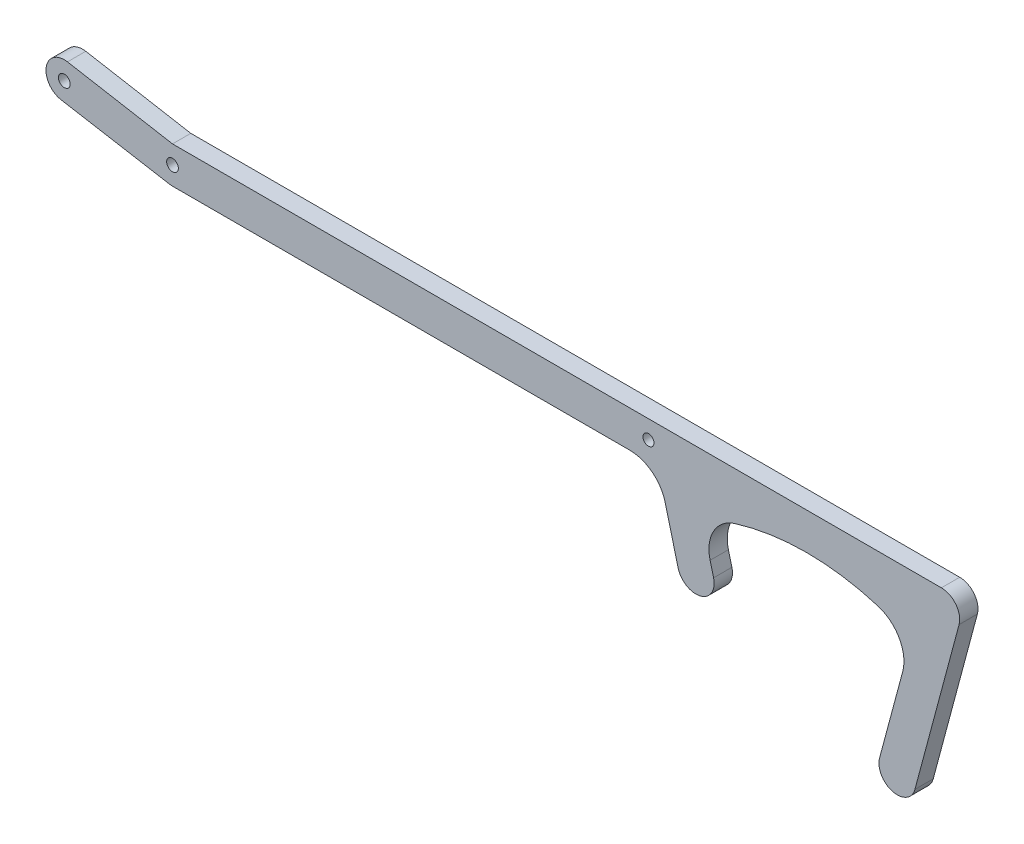
SolidWorks part; units mm, degrees
ref_plane "Front Plane" through (0, 0, 0) normal (0, 0, 1) x (1, 0, 0)
ref_plane "Top Plane" through (0, 0, 0) normal (0, 1, 0) x (1, 0, 0)
ref_plane "Right Plane" through (0, 0, 0) normal (1, 0, 0) x (0, 0, -1)
sketch "Sketch1" plane through (0, 0, 0) normal (0, 0, 1) x (1, 0, 0)
  line L0 (0, 0) -> (266.7, 0) construction
  line L1 (0, 6.35) -> (266.7, 6.35)
  line L2 (0, -6.35) -> (168.4202, -6.35)
  line L3 (272.8336, -1.6435) -> (257.5203, -58.7935)
  line L4 (245.2531, -55.5065) -> (256.2126, -14.605)
  line L6 (175.3883, -33.3375) -> (168.4202, -6.35)
  line L7 (187.6851, -30.1625) -> (183.6681, -14.605)
  line L8 (0, 0) -> (-37.5378, 6.521) construction
  line L10 (0, 6.35) -> (-36.4351, 12.7745)
  line L11 (-38.6246, 0.2647) -> (-1.0868, -6.2563)
  circle A0 centre (0, 0) radius 2.032
  arc A2 (272.8336, -1.6435) -> (266.7, 6.35) centre (266.7, 0) ccw
  arc A3 (245.2531, -55.5065) -> (257.5203, -58.7935) centre (251.3867, -57.15) ccw
  arc A5 (175.3883, -33.3375) -> (187.6851, -30.1625) centre (181.5367, -31.75) ccw
  arc A6 (183.6681, -14.605) -> (256.2126, -14.605) centre (219.9404, -90.8741) cw
  circle A7 centre (165.1, 0) radius 1.905
  arc A9 (-36.4351, 12.7745) -> (-38.6246, 0.2647) centre (-37.5378, 6.521) ccw
  circle A10 centre (-37.5378, 6.521) radius 2.032
  arc A12 (0, -6.35) -> (-1.0868, -6.2563) centre (0, 0) cw
  dimension "D1" = 31.75
  dimension "D3" = 6.35
  dimension "D5" = 6.35
  dimension "D6" = 6.35
  dimension "D11" = 4.064
  dimension "D14" = 17.145
  dimension "D10" = 75
  dimension "D13" = 84.455
  dimension "D15" = 3.81
  dimension "D19" = 6.35
  dimension "D21" = 4.064
  dimension "D17" = 6.35
  dimension "D4" = 12.7
  dimension "D7" = 266.7
  dimension "D8" = 57.15
  dimension "D9" = 69.85
  dimension "D12" = 26.9875
  dimension "D16" = 165.1
  dimension "D18" = 38.1
  dimension "D20" = 170
extrude "Boss-Extrude1" add sketch "Sketch1" along normal mid plane 6.35
fillet "Fillet1" radius 12.7 1 edges at (168.4202, -6.35, 0)
fillet "Fillet2" radius 12.7 2 edges at (256.2126, -14.605, 0) (183.6681, -14.605, 0)
